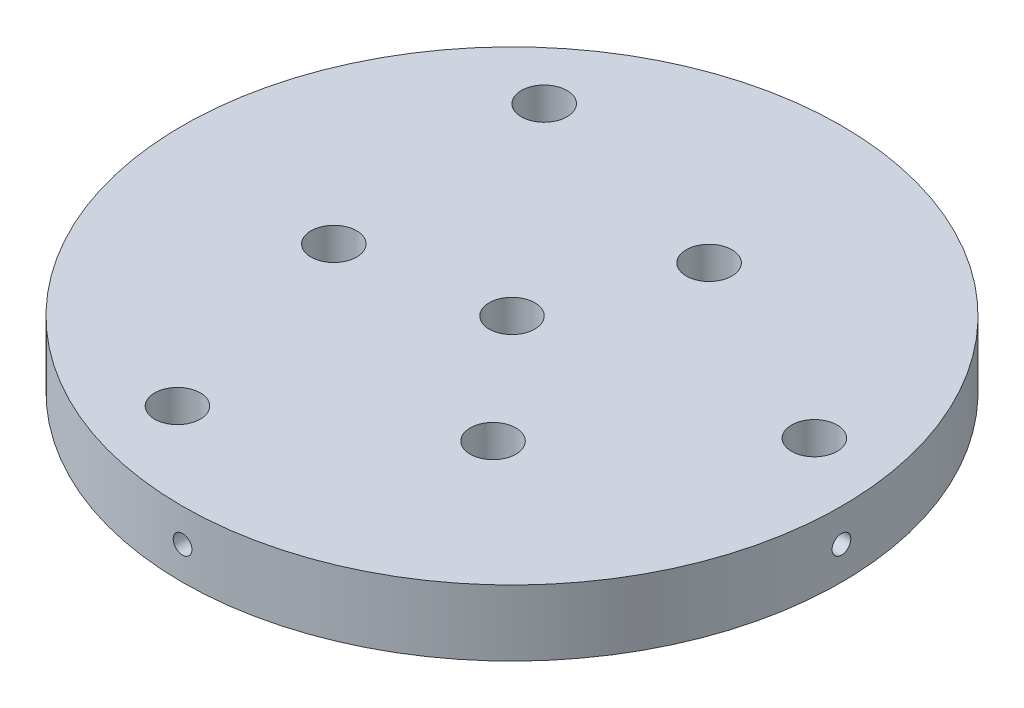
SolidWorks part; units mm, degrees
ref_plane "Front Plane" through (0, 0, 0) normal (0, 0, 1) x (1, 0, 0)
ref_plane "Top Plane" through (0, 0, 0) normal (0, 1, 0) x (1, 0, 0)
ref_plane "Right Plane" through (0, 0, 0) normal (1, 0, 0) x (0, 0, -1)
sketch "Sketch1" plane through (0, 0, 0) normal (0, 1, 0) x (1, 0, 0)
  circle A0 centre (0, 0) radius 47.625
  circle A1 centre (0, 0) radius 3.3
  circle A2 centre (0, 25.4) radius 1.5875 construction
  dimension "D1" = 95.25
  dimension "D2" = 6.6
  dimension "D3" = 3.175
  dimension "D4" = 25.4
extrude "Boss-Extrude1" add sketch "Sketch1" along normal mid plane 9.525
ref_plane "Plane1" through (0, 0, 50.8) normal (0, 0, 1) x (1, 0, 0)
sketch "Sketch2" plane through (0, 0, 50.8) normal (0, 0, 1) x (1, 0, 0)
  circle A0 centre (0, 0) radius 1.3526
  dimension "D1" = 2.7051
extrude "Cut-Extrude1" cut sketch "Sketch2" against normal blind 12.7
sketch "Sketch3" plane through (0, 0, 0) normal (0, 0, 1) x (1, 0, 0)
  line L0 (0, 4.7625) -> (0, -4.7625)
  line L1 (47.625, 4.7625) -> (-47.625, 4.7625) construction
  line L2 (-47.625, -4.7625) -> (47.625, -4.7625) construction
pattern_circular "CirPattern1" count 4 over 360 about axis through (0, 4.7625, 0) along (0, -1, 0) of "Cut-Extrude1"
sketch "Sketch4" plane through (0, 4.7625, 0) normal (0, 1, 0) x (1, 0, 0)
  line L0 (0, 0) -> (0, -35.975) construction
  line L1 (-12.9007, -35.4443) -> (0, 0) construction
  line L2 (0, 0) -> (14.286, -17.0253) construction
  circle A0 centre (-12.9007, -35.4443) radius 3.3
  circle A1 centre (-24.2453, 28.8944) radius 3.3
  circle A2 centre (37.146, 6.5498) radius 3.3
  circle A3 centre (14.286, -17.0253) radius 3.3
  circle A4 centre (-21.8874, -3.8593) radius 3.3
  circle A5 centre (7.6014, 20.8847) radius 3.3
  point P12 (0, 0)
  point P19 (0, 0)
  dimension "D1" = 6.6
  dimension "D7" = 6.6
  dimension "D2" = 37.719
  dimension "D3" = 20
  dimension "D5" = 60
  dimension "D6" = 22.225
  dimension "D4" = 3
  dimension "D8" = 3
extrude "Cut-Extrude2" cut sketch "Sketch4" against normal through all
equation "\"Body_Tube_OD\"= 4.024in"
equation "\"Body_Tube_ID\"= 3.90in"
equation "\"SS_Fwd_Bulkhead_OD\"=3.75"
equation "\"D1@Sketch1\"=\"SS_Fwd_Bulkhead_OD\""
equation "\"Bodytube_OD\" = 6.17in"
equation "\"Bodytube_ID\" = 5.998in"
equation "\"Motor_OD\" = 4in"
equation "\"Fwd_Tube_Length\" = 40in"
equation "\"Mid_Tube_Length\" = 1in"
equation "\"Mid_Coupler_Length\" = 13in"
equation "\"Aft_Section_Length\"= 39in"
equation "\"AB_Coupler_OD_Length\"= 1in"
equation "\"AB_Coupling_Section_Length\"= 0.375in"
equation "\"AB_Coupler_Length\"= \"AB_Coupler_OD_Length\" + \"AB_Coupling_Section_Length\" * 2"
equation "\"Cutout_Angle\" = 80"
equation "\"AB_Paddle_Height\" = 0.375in"
equation "\"AB_Coupler_Num_Screws\"= 6"
equation "\"AB_BKHD_Thickness\" = 0.375in"
equation "\"AB_Mount_From_Bottom\" = 23.175in"
equation "\"Num_Cutouts\" = 3"
equation "\"AB_Coupler_OD\"= 6.17in"
equation "\"AB_Coupler_ID\"= 5.75in"
equation "\"AB_Coupler_Surface_Diameter\"= 5.998in"
equation "\"AB_Coupling_Screw_Diameter\"= 0.1065in"
equation "\"AB_Central_Bushing_Length\" = .75in"
equation "\"Lead_Screw_Dist\" = 2.25in"
equation "\"Lead_Screw_Diam\" = 11mm"
equation "\"Lead_Screw_Length\" = (\"Mid_Coupler_Length\" + 2*0.375in + 2*0.5in)"
equation "\"Paddle_Pin_Offset\" = .25in"
equation "\"Paddle_Pin_Radius\" = 2.25in"
equation "\"SS_Paddle_Pin_Radius\" = 2.25*0.66in"
equation "\"Paddle_Gear_OD\" = 3.2in"
equation "\"Drive_Gear_OD\" = 1.7in"
equation "\"Fwd_BKHD_From_Top\" = 18in"
equation "\"Fin_Thickness\"= .118in"
equation "\"Guiderail_Cutout_Diameter\"= 1.5in"
equation "\"DB9_Hole_Dist\" = 25mm"
equation "\"DB9_Relief_Width\" = 0.47in"
equation "\"DB9_Relief_Hole_Offset\" = 0.09in"
equation "\"Airbrakes_Wire_Hole_Dia\" = .25in"
equation "\"Airbrakes_Wire_Hole_Dist\" = 1.1in"
equation "\"Servo_Gear_Offset\" = 0.5in"
